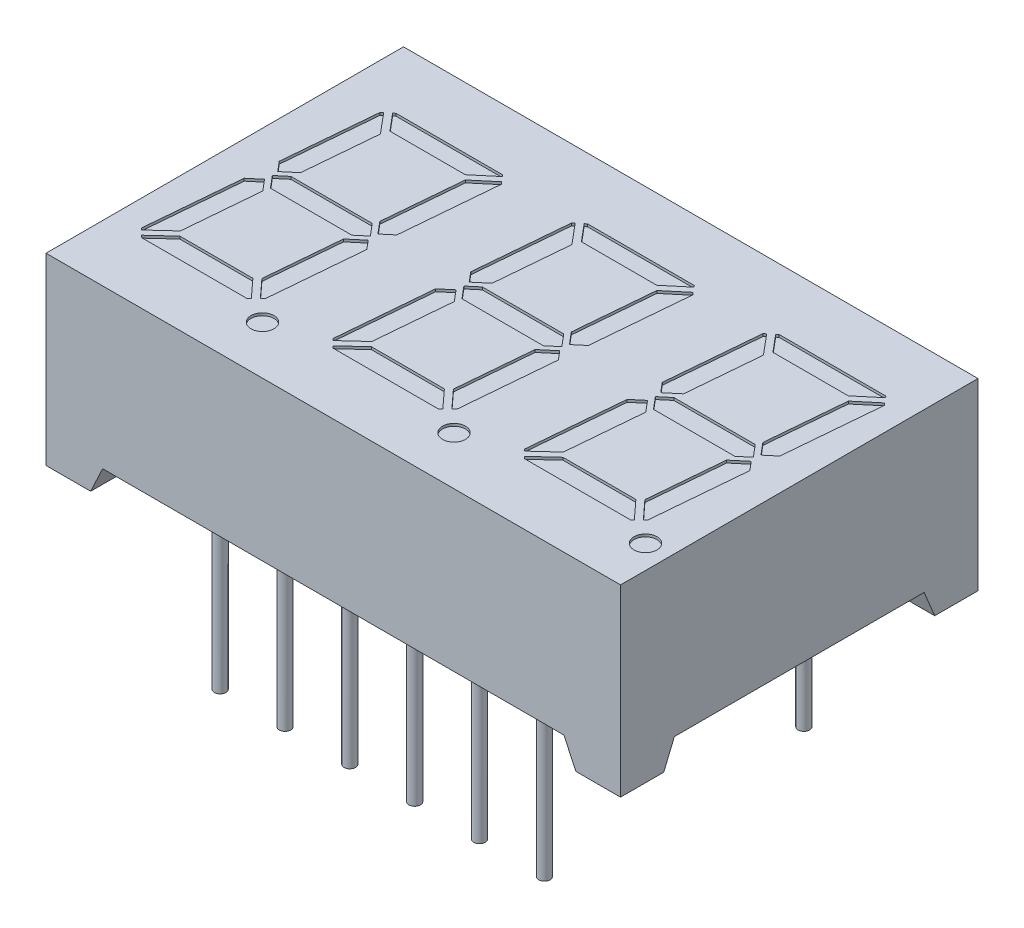
SolidWorks part; units mm, degrees
ref_plane "Front Plane" through (0, 0, 0) normal (0, 0, 1) x (1, 0, 0)
ref_plane "Top Plane" through (0, 0, 0) normal (0, 1, 0) x (1, 0, 0)
ref_plane "Right Plane" through (0, 0, 0) normal (1, 0, 0) x (0, 0, -1)
sketch "Sketch1" plane through (0, 0, 0) normal (0, 1, 0) x (1, 0, 0)
  line L0 (-11.25, 7) -> (11.25, -7) construction
  line L1 (-11.25, 7) -> (11.25, 7)
  line L2 (-11.25, 7) -> (-11.25, -7)
  line L3 (-11.25, -7) -> (11.25, -7)
  line L4 (11.25, 7) -> (11.25, -7)
  dimension "D1" = 22.5
  dimension "D2" = 14
extrude "Extrude1" add sketch "Sketch1" against normal blind 7.2 contours L3 L4 L1 L2
sketch "Sketch6" plane through (0, 0, 0) normal (0, 1, 0) x (-1, 0, 0)
  line L0 (1.6151, 0.6456) -> (1.875, 3.6157)
  line L1 (-1.2882, 4.1767) -> (-1.608, 0.5204) construction
  line L2 (-2.0851, 4.2464) -> (-2.405, 0.5901)
  line L3 (-2.752, -4.347) -> (-2.8289, -4.2553)
  line L4 (0, 0) -> (11.25, 0) construction
  line L5 (-2.5913, -4.5385) -> (-1.7979, -3.8728)
  line L6 (1.7257, 0) -> (0, 0) construction
  line L7 (1.5602, -0.4) -> (1.9541, -0.0695)
  line L8 (1.5602, 0.4) -> (-1.6271, 0.4)
  line L10 (-1.7979, -3.8728) -> (1.1546, -3.8728)
  line L11 (2.4951, 4.523) -> (2.4181, 4.6)
  line L12 (-1.7074, -0.6155) -> (-1.977, -3.6967)
  line L13 (1.7132, -4.5385) -> (1.1546, -3.8728)
  line L14 (-1.1516, 3.8) -> (-1.8114, 4.5201)
  line L15 (-1.3359, 3.6311) -> (-1.9884, 4.3432)
  line L16 (-2.4993, -0.4882) -> (-2.8289, -4.2553)
  line L17 (-1.9884, 4.3432) -> (-2.0851, 4.2464)
  line L18 (1.7061, 3.8) -> (2.4951, 4.523)
  line L19 (1.875, 3.6157) -> (2.6721, 4.3461)
  line L20 (-2.0973, -0.1508) -> (-1.7074, -0.6155)
  line L21 (-2.0973, -0.1508) -> (-2.4993, -0.4882)
  line L22 (1.9541, -0.0695) -> (1.5602, 0.4)
  line L23 (-1.6271, -0.4) -> (-2.0211, 0.0695)
  line L24 (-1.3359, 3.6311) -> (-1.5932, 0.6895)
  line L25 (-2.0211, 0.0695) -> (-1.6271, 0.4)
  line L26 (11.25, -7) -> (11.25, 7) construction
  line L27 (1.5602, -0.4) -> (-1.6271, -0.4)
  line L28 (1.9829, -0.3064) -> (2.3017, -0.6864)
  line L29 (1.4961, -0.7148) -> (1.9829, -0.3064)
  line L30 (1.9788, 0.2123) -> (2.4121, 0.5759)
  line L31 (-1.7024, -0.5579) -> (-2.032, -4.325) construction
  line L32 (1.9846, -4.3107) -> (2.3017, -0.6864)
  line L33 (-0.4499, -4.6) -> (0, 0.5424) construction
  line L34 (11.25, -7) -> (-11.25, -7) construction
  line L35 (0, 0) -> (0, -7) construction
  line L36 (1.9047, -4.3778) -> (1.2445, -3.591)
  line L37 (1.9788, 0.2123) -> (1.6151, 0.6456)
  line L38 (2.4121, 0.5759) -> (2.7363, 4.2818)
  line L39 (1.6151, 0.6456) -> (1.9394, 4.3515) construction
  line L40 (-2.1186, 0.2487) -> (-2.405, 0.5901)
  line L41 (-1.5932, 0.6895) -> (-2.1186, 0.2487)
  line L42 (2.4181, 4.6) -> (-1.7316, 4.6)
  line L43 (-1.9924, -3.8728) -> (-2.8591, -4.6) construction
  line L44 (1.7061, 3.8) -> (-1.1516, 3.8)
  line L46 (1.9234, -4.5946) -> (1.0214, -3.5196) construction
  line L47 (1.9756, 3.7078) -> (1.8067, 3.8922) construction
  line L48 (2.8486, 4.5078) -> (2.6797, 4.6922) construction
  line L49 (2.7642, 4.6) -> (1.8911, 3.8) construction
  line L50 (1.2445, -3.591) -> (1.4961, -0.7148)
  line L52 (-1.3211, 3.8) -> (-2.0542, 4.6) construction
  line L53 (1.9846, -4.3107) -> (1.9047, -4.3778)
  line L54 (-2.5397, -4.6) -> (-2.5913, -4.5385)
  line L55 (2.7363, 4.2818) -> (2.6721, 4.3461)
  line L56 (-1.7316, 4.6) -> (-1.8114, 4.5201)
  line L57 (1.7132, -4.5385) -> (1.6398, -4.6)
  line L58 (-2.752, -4.347) -> (-1.977, -3.6967)
  line L59 (-2.5397, -4.6) -> (1.6398, -4.6)
  circle A0 centre (-2.8289, 5.1) radius 0.45
  dimension "D16" = 0.9
  dimension "D6" = 9.2
  dimension "D8" = 4.8
  dimension "D9" = 0.2
  dimension "D10" = 0.8
  dimension "D11" = 0.2
  dimension "D12" = 0.2
  dimension "D13" = 0.25
  dimension "D14" = 0.25
  dimension "D15" = 5.1
  dimension "D17" = 0.2
  dimension "D19" = 0.2
  dimension "D22" = 0.25
  dimension "D23" = 0.25
  dimension "D25" = 0.45
  dimension "D26" = 45
  dimension "D28" = 0.45
  dimension "D29" = 0.45
  dimension "D31" = 0.5
  dimension "D5" = 5
  dimension "D7" = 4.6
  dimension "D4" = 0.8
extrude "Cut-Extrude1" cut sketch "Sketch6" against normal blind 0.1
sketch "Sketch12" plane through (-11.25, 0, 0) normal (-1, 0, 0) x (0, 0, 1)
  line L0 (-5.305, -7.2) -> (-4.8908, -6.2)
  line L1 (-4.8908, -6.2) -> (4.8908, -6.2)
  line L2 (4.8908, -6.2) -> (5.305, -7.2)
  line L4 (0, -3.96) -> (0, 3.96) construction
  line L5 (-7, -7.2) -> (7, -7.2) construction
  point P2 (0, -6.2)
  dimension "D1" = 1
  dimension "D2" = 45
  dimension "D3" = 10.61
extrude "Cut-Extrude2" cut sketch "Sketch12" against normal through all and the other way through all flip side to cut
sketch "Sketch13" plane through (0, 0, -7) normal (0, 0, -1) x (-1, 0, 0)
  line L0 (-9.5, -7.2) -> (-9.0337, -6.2)
  line L1 (11.25, -7.2) -> (-11.25, -7.2) construction
  line L2 (-9.0337, -6.2) -> (9.0337, -6.2)
  line L3 (9.0337, -6.2) -> (9.5, -7.2)
  line L4 (0, 3.96) -> (0, -3.96) construction
  line L5 (11.25, -6.2) -> (-11.25, -6.2) construction
  point P4 (0, -6.2)
  dimension "D1" = 19
  dimension "D2" = 50
extrude "Cut-Extrude3" cut sketch "Sketch13" against normal through all and the other way through all flip side to cut
pattern_linear "LPattern1" count 2 spacing 7.5 along (1, 0, 0) of "Cut-Extrude1"
pattern_linear "LPattern2" count 2 spacing 7.5 along (-1, 0, 0) of "Cut-Extrude1"
sketch "Sketch11" plane through (0, -7.2, 0) normal (0, -1, 0) x (1, 0, 0)
  line L0 (0, -3.96) -> (0, 3.96) construction
  line L1 (3.96, 0) -> (-3.96, 0) construction
  circle A0 centre (6.35, 5.08) radius 0.225
  dimension "D2" = 0.45
  dimension "D1" = 6.35
  dimension "D3" = 5.08
extrude "Boss-Extrude4" add sketch "Sketch11" along normal blind 6.1 and the other way up to next
pattern_linear "LPattern3" count 6 spacing 2.54 along (-1, 0, 0) count 2 spacing 10.16 along (0, 0, -1) of "Boss-Extrude4"
